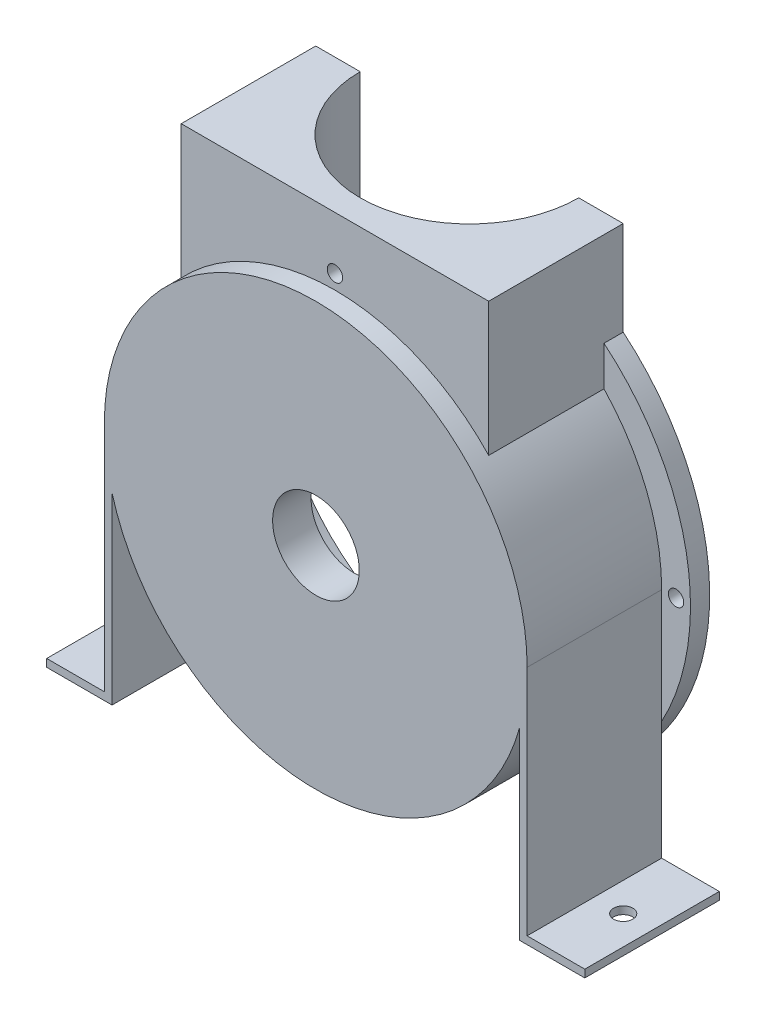
SolidWorks part; units mm, degrees
ref_plane "Спереди" through (0, 0, 0) normal (0, 0, 1) x (1, 0, 0)
ref_plane "Сверху" through (0, 0, 0) normal (0, 1, 0) x (1, 0, 0)
ref_plane "Справа" through (0, 0, 0) normal (1, 0, 0) x (0, 0, -1)
other "Configuration Table"
sketch "Sketch1" plane through (0, 0, 0) normal (0, 0, 1) x (1, 0, 0)
  line L1 (0, 0) -> (200, 0)
  line L2 (0, 0) -> (0, 135)
  line L3 (0, 135) -> (200, 135)
  line L4 (200, 0) -> (200, 135)
  dimension "D1" = 200
  dimension "D2" = 135
extrude "Boss-Extrude1" add sketch "Sketch1" along normal blind 40
sketch "Sketch6" plane through (0, 0, 40) normal (0, 0, 1) x (1, 0, 0)
  line L0 (100, 62.5) -> (140, 62.5)
  line L1 (0, 0) -> (100, 0)
  line L2 (0, 0) -> (0, 62.5)
  line L3 (0, 62.5) -> (100, 62.5)
  line L4 (100, 0) -> (100, 62.5)
  line L5 (140, 62.5) -> (140, 137.7853)
  line L6 (140, 137.7853) -> (60, 137.7853)
  line L7 (60, 137.7853) -> (60, 62.5)
  line L8 (60, 62.5) -> (100, 62.5)
  circle A0 centre (100, 62.5) radius 62.5
  line M8 (0, 135) -> (0, 0)
  line M9 (0, 0) -> (200, 0)
  line M10 (200, 0) -> (200, 135)
  line M11 (200, 135) -> (0, 135)
  dimension "D1" = 100
  dimension "D2" = 62.5
  dimension "D3" = 40
  dimension "D4" = 40
extrude "Cut-Extrude2" cut sketch "Sketch6" against normal blind 40 contours A0 L7 L3 M11 M8 | A0 L3 M8 M9 | A0 L5 M9 M10 M11 region at (27.3674, 26.6952, 40) region at (173.5441, 66.8996, 40) region at (25.65, 102.4466, 40)
sketch "Sketch7" plane through (0, 0, 40) normal (0, 0, 1) x (1, 0, 0)
  line L1 (60, 62.5) -> (140, 62.5)
  line L2 (60, 62.5) -> (60, 137.7853)
  line L3 (60, 137.7853) -> (140, 137.7853)
  line L4 (140, 62.5) -> (140, 137.7853)
  circle A0 centre (100, 62.5) radius 55
  arc M5 (60, 110.5234) -> (140, 110.5234) centre (100, 62.5) ccw
extrude "Cut-Extrude3" cut sketch "Sketch7" against normal blind 35 contours A0 L2 L4 M5 region at (79.0738, 9.8368, 40)
sketch "Sketch8" plane through (0, 0, 40) normal (0, 0, 1) x (1, 0, 0)
  line L1 (60, 62.5) -> (140, 62.5)
  line L2 (60, 62.5) -> (60, 137.7853)
  line L3 (60, 137.7853) -> (140, 137.7853)
  line L4 (140, 62.5) -> (140, 137.7853)
  circle A0 centre (100, 62.5) radius 55
  line M2 (140, 100.2492) -> (140, 135)
  line M3 (140, 135) -> (60, 135)
  line M4 (60, 135) -> (60, 100.2492)
extrude "Cut-Extrude4" cut sketch "Sketch8" against normal blind 5 contours A0 M2 M3 M4 region at (100, 123.0387, 40)
sketch "Sketch9" plane through (0, 0, 0) normal (0, 0, -1) x (-1, 0, 0)
  line L0 (-140, 135) -> (-60, 135) construction
  line L1 (-100, 62.5) -> (-71.8, 62.5)
  line L2 (-100, 62.5) -> (-100, 135)
  line L3 (-100, 135) -> (-71.8, 135)
  line L4 (-71.8, 62.5) -> (-71.8, 135)
  line L6 (-100, 62.5) -> (-128.2, 62.5)
  line L7 (-100, 62.5) -> (-100, 135)
  line L8 (-100, 135) -> (-128.2, 135)
  line L9 (-128.2, 62.5) -> (-128.2, 135)
  circle A0 centre (-100, 62.5) radius 50
  dimension "D1" = 28.2
  dimension "D2" = 28.2
extrude "Cut-Extrude5" cut sketch "Sketch9" against normal blind 28.2 contours L9 A0 L4 L1 L6 | L2 A0 L9 L6 | L4 A0 L2 L1 region at (86.325, 86.1722, 0) region at (113.675, 86.1722, 0) region at (100, 50.3602, 0)
sketch "Sketch10" plane through (0, 0, 40) normal (0, 0, 1) x (1, 0, 0)
  line L0 (100, 62.5) -> (155, 62.5)
  line L1 (60, 62.5) -> (140, 62.5) construction
  line L2 (155, 62.5) -> (155, 0)
  line L3 (155, 0) -> (170, 0)
  line L4 (170, 0) -> (170, 2)
  line L5 (170, 2) -> (153, 2)
  line L6 (153, 2) -> (153, 0)
  line L7 (153, 0) -> (155, 0)
  line L8 (153, 2) -> (153, 48.3034)
  line L9 (100, 62.5) -> (45, 62.5)
  line L10 (45, 62.5) -> (45, 2)
  line L11 (45, 2) -> (30, 2)
  line L12 (30, 2) -> (30, 0)
  line L13 (30, 0) -> (47, 0)
  line L14 (47, 0) -> (47, 64.3434)
  circle A0 centre (100, 62.5) radius 55 construction
  circle A1 centre (100, 62.5) radius 55
  circle M11 centre (100, 62.5) radius 55
  dimension "D1" = 2
  dimension "D2" = 2
  dimension "D3" = 17
  dimension "D4" = 2
  dimension "D5" = 2
  dimension "D6" = 17
  dimension "D7" = 110
extrude "Boss-Extrude2" add sketch "Sketch10" against normal blind 35 contours L6 L7 L2 L5 | L4 L5 L2 L3 | L8 L5 L2 M11 | L13 L14 L10 L11 L12 M11 region at (154.0386, 27.4509, 40) region at (162.5, 1, 40) region at (154, 1, 40) region at (45.4381, 55.0751, 40)
sketch "Sketch12" plane through (0, 135, 0) normal (0, 1, 0) x (1, 0, 0)
  line L1 (60, 0) -> (100, 0)
  line L2 (60, 0) -> (60, -17.5)
  line L3 (60, -17.5) -> (100, -17.5)
  line L4 (100, 0) -> (100, -17.5)
  circle A0 centre (100, 0) radius 28.2
  line M3 (140, 0) -> (60, 0)
extrude "Cut-Extrude6" cut sketch "Sketch12" against normal blind 35 contours L3 A0 L4 M3 | A0 L3 L4 M3 region at (86.8059, 135, 8.4208) region at (107.6825, 135, 14.0341)
sketch "Sketch15" plane through (0, 0, 0) normal (0, 0, -1) x (-1, 0, 0)
  line L0 (-100, 62.5) -> (-162.5, 62.5)
  line L1 (-45, 62.5) -> (-37.5, 62.5)
  circle A0 centre (-100, 62.5) radius 62.5
  circle A1 centre (-100, 62.5) radius 50
  circle A2 centre (-100, 62.5) radius 55 construction
  circle A3 centre (-41.25, 62.5) radius 2
extrude "Cut-Extrude8" cut sketch "Sketch15" against normal blind 35 contours A3
pattern_circular "CirPattern1" count 4 over 360 about axis through (100, 62.5, 5) along (0, 0, 1) of "Cut-Extrude8"
sketch "Sketch16" plane through (0, 2, 0) normal (0, 1, 0) x (1, 0, 0)
  line L1 (170, -40) -> (162.5, -40)
  line L2 (170, -40) -> (170, -22.5)
  line L3 (170, -22.5) -> (162.5, -22.5)
  line L4 (162.5, -40) -> (162.5, -22.5)
  line L5 (30, -5) -> (37.5, -5)
  line L6 (30, -5) -> (30, -22.5)
  line L7 (30, -22.5) -> (37.5, -22.5)
  line L8 (37.5, -5) -> (37.5, -22.5)
  circle A0 centre (162.5, -22.5) radius 2.5
  circle A1 centre (37.5, -22.5) radius 2.5
  dimension "D3" = 17.5
  dimension "D1" = 7.5
  dimension "D2" = 17.5
  dimension "D4" = 7.5
extrude "Cut-Extrude9" cut sketch "Sketch16" against normal blind 35 contours A0 | A1
sketch "Sketch17" plane through (0, 135, 0) normal (0, 1, 0) x (1, 0, 0)
  circle A0 centre (100, 0) radius 30.2
extrude "Cut-Extrude10" cut sketch "Sketch17" against normal blind 38
sketch "Sketch18" plane through (0, 135, 0) normal (0, 1, 0) x (1, 0, 0)
  line L0 (150, 0) -> (50, 0) construction
  line L1 (60, 0) -> (140, 0)
  circle A0 centre (100, 0) radius 32.2
  arc M3 (130.2, 0) -> (69.8, 0) centre (100, 0) cw
  dimension "D1" = 64.4
extrude "Boss-Extrude3" add sketch "Sketch18" against normal blind 34 contours L1 M3 region at (100, 135, 12.8173)
sketch "Sketch19" plane through (0, 135, 0) normal (0, 1, 0) x (1, 0, 0)
  line L0 (150, 0) -> (50, 0) construction
  circle A0 centre (100, 0) radius 28.43
  dimension "D1" = 56.86
extrude "Cut-Extrude11" cut sketch "Sketch19" against normal blind 41
sketch "Sketch20" plane through (0, 0, 0) normal (0, 0, -1) x (-1, 0, 0)
  circle A0 centre (-100, 62.5) radius 51
extrude "Cut-Extrude12" cut sketch "Sketch20" against normal blind 30
scale "Scale6" scale about centroid uniform scaling yes scale factor 1.33
sketch "Sketch23" plane through (0, 0, 31.2865) normal (0, 0, -1) x (-1, 0, 0)
  circle A0 centre (-100.0692, 59.9064) radius 15
extrude "Cut-Extrude15" cut sketch "Sketch23" against normal through all
